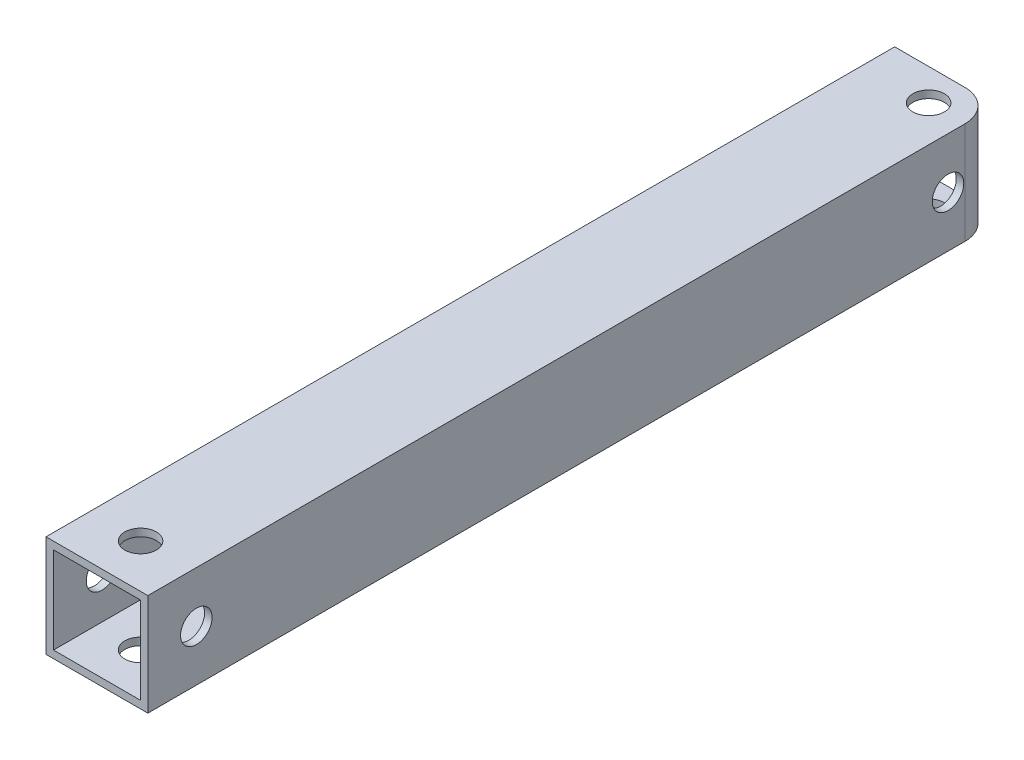
SolidWorks part; units mm, degrees
ref_plane "Alzado" through (0, 0, 0) normal (0, 0, 1) x (1, 0, 0)
ref_plane "Planta" through (0, 0, 0) normal (0, 1, 0) x (1, 0, 0)
ref_plane "Vista lateral" through (0, 0, 0) normal (1, 0, 0) x (0, 0, -1)
sketch "Croquis1" plane through (0, 0, 0) normal (0, 0, 1) x (1, 0, 0)
  line L1 (21, -21) -> (-21, -21)
  line L2 (21, -21) -> (21, 21)
  line L3 (21, 21) -> (-21, 21)
  line L4 (-21, -21) -> (-21, 21)
  line L5 (21, -21) -> (-21, 21) construction
  line L6 (21, 21) -> (-21, -21) construction
  point P0 (0, 0)
  point P6 (-21, 0)
  dimension "D1" = 42
  dimension "D2" = 42
extrude "Saliente-Extruir1" add sketch "Croquis1" along normal mid plane 350
sketch3d "Croquis3D1"
  line L0 (-17.9, -17.9, 175) -> (17.9, -17.9, 175)
  line L1 (17.9, -17.9, 175) -> (17.9, 17.9, 175)
  line L2 (17.9, 17.9, 175) -> (-17.9, 17.9, 175)
  line L3 (-17.9, 17.9, 175) -> (-17.9, -17.9, 175)
  line L4 (-17.9, -17.9, 175) -> (17.9, -17.9, 175)
  line L5 (17.9, -17.9, 175) -> (17.9, 17.9, 175)
  line L6 (17.9, 17.9, 175) -> (-17.9, 17.9, 175)
  line L7 (-17.9, 17.9, 175) -> (-17.9, -17.9, 175)
  dimension "D1" = 3.1
extrude "Cortar-Extruir1" cut sketch "Croquis3D1" along direction (0, 0, 1) on the side against the normal through all
sketch "Croquis2" plane through (-21, 0, 0) normal (-1, 0, 0) x (0, 0, 1)
  line L1 (175, -17.9) -> (-175, -17.9)
  line L2 (175, -17.9) -> (175, 17.9)
  line L3 (175, 17.9) -> (-175, 17.9)
  line L4 (-175, 21) -> (-175, -21)
  line L5 (-175, -21) -> (175, -21)
  line L6 (175, -21) -> (175, 21)
  line L7 (175, 21) -> (-175, 21)
  line L8 (-175, 21) -> (-175, -21)
  line L9 (-175, -21) -> (175, -21)
  line L10 (175, -21) -> (175, 21)
  line L11 (175, 21) -> (-175, 21)
  line L12 (-175, -17.9) -> (-175, 17.9)
  line L13 (175, -17.9) -> (-175, 17.9) construction
  line L14 (175, 17.9) -> (-175, -17.9) construction
  point P2 (0, 0)
  dimension "D2" = 3.1
  dimension "D1" = 0
sketch "Croquis3" plane through (0, -21, 0) normal (0, -1, 0) x (1, 0, 0)
  line L0 (-21, 175) -> (21, 175) construction
  line L1 (0, 166.4406) -> (0, -46.6838) construction
  circle A0 centre (0, 157) radius 6.5
  dimension "D1" = 13
  dimension "D2" = 18
extrude "Cortar-Extruir3" cut sketch "Croquis3" against normal blind 60 contours A0
sketch "Croquis4" plane through (21, 0, 0) normal (1, 0, 0) x (0, 0, -1)
  line L0 (155, 42.844) -> (155, -60.1919) construction
  line L1 (180.7653, 0) -> (-212.4531, 0) construction
  line L2 (175, 21) -> (175, -21) construction
  circle A0 centre (155, 0) radius 6.5
  dimension "D1" = 13
  dimension "D2" = 20
extrude "Cortar-Extruir4" cut sketch "Croquis4" against normal blind 70
sketch "Croquis5" plane through (0, 21, 0) normal (0, 1, 0) x (1, 0, 0)
  line L0 (0, 173.2825) -> (0, -26.5385) construction
  line L1 (21, 175) -> (-21, 175) construction
  line L2 (6, 163.2061) -> (6, 116.6333) construction
  circle A0 centre (6, 162) radius 6.5
  dimension "D1" = 13
  dimension "D2" = 13
  dimension "D3" = 6
extrude "Cortar-Extruir5" cut sketch "Croquis5" against normal through all
fillet "Redondeo1" radius 13 1 edges at (21, 0, -175)
sketch "Croquis6" plane through (-21, 0, 0) normal (-1, 0, 0) x (0, 0, 1)
  line L0 (168.557, 0) -> (114.2629, 0) construction
  line L1 (175, 21) -> (175, -21) construction
  circle A0 centre (155, 0) radius 6.5
  dimension "D2" = 13
  dimension "D1" = 20
extrude "Cortar-Extruir6" cut sketch "Croquis6" against normal blind 60
